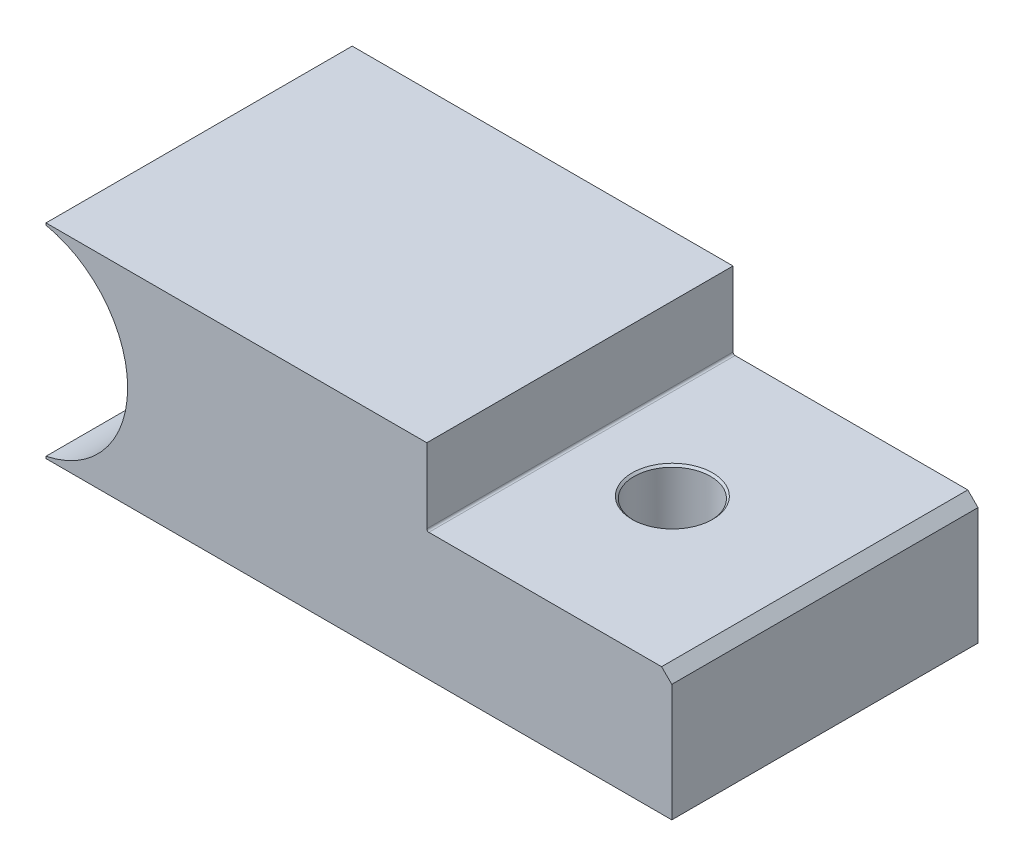
SolidWorks part; units mm, degrees
material "AISI Type A2 Tool Steel Custom"
ref_plane "Front Plane" through (0, 0, 0) normal (0, 0, 1) x (1, 0, 0)
ref_plane "Top Plane" through (0, 0, 0) normal (0, 1, 0) x (1, 0, 0)
ref_plane "Right Plane" through (0, 0, 0) normal (1, 0, 0) x (0, 0, -1)
sketch "Sketch1" plane through (0, 0, 0) normal (0, 0, 1) x (1, 0, 0)
  line L1 (2.54, 0) -> (80.4026, 0)
  line L3 (2.54, 25.4) -> (49.9226, 25.4)
  line L4 (80.4026, 0) -> (80.4026, 15.875)
  line L5 (2.54, 25.4) -> (2.54, 25.1434)
  line L6 (49.9226, 25.4) -> (49.9226, 15.875)
  line L7 (49.9226, 15.875) -> (80.4026, 15.875)
  line L8 (2.54, 0.2566) -> (2.54, 0)
  arc A1 (2.54, 0.2566) -> (2.54, 25.1434) centre (0, 12.7) ccw
  dimension "D2" = 25.4
  dimension "D1" = 47.3826
  dimension "D3" = 9.525
  dimension "D4" = 2.54
  dimension "D5" = 30.48
  dimension "D6" = 15.875
  dimension "D7" = 0.2566
extrude "Boss-Extrude1" add sketch "Sketch1" along normal blind 38.1
sketch "Sketch2" plane through (0, 15.875, 0) normal (0, 1, 0) x (1, 0, 0)
  line L0 (0, -38.1) -> (0, 0) construction
  line L1 (2.54, -38.1) -> (2.54, 0) construction
  point P0 (61.4256, -19.05)
  point P5 (0, -19.05)
  point P8 (2.54, -19.05)
  dimension "D1" = 61.4256
hole_wizard "3/8 (0.375) Diameter Hole1" positions "Sketch2" profile "Sketch4" hole size "3/8" standard "ANSI Inch" end condition through all
sketch "Sketch4" plane through (61.4256, 15.875, 19.05) normal (1, 0, 0) x (0, 0, 1)
  line L0 (0, 0) -> (0, 15.875)
  line L1 (0, 15.875) -> (4.7625, 15.875)
  line L2 (4.7625, 15.875) -> (4.7625, 0)
  line L5 (4.7625, 0) -> (0, 0)
  line L11 (0, -6.35) -> (0, 107.95) construction
  dimension "Thru Hole Dia." = 9.525
  dimension "Thru Hole Depth" = 15.875
chamfer "Chamfer1" distance 1.27 angle 45 1 edges at (80.4026, 15.875, 19.05)
chamfer "Chamfer2" distance 0.254 angle 45 1 edges at (61.4256, 15.875, 23.8125)
fillet "Fillet1" radius 0.254 1 edges at (49.9226, 15.875, 19.05)
